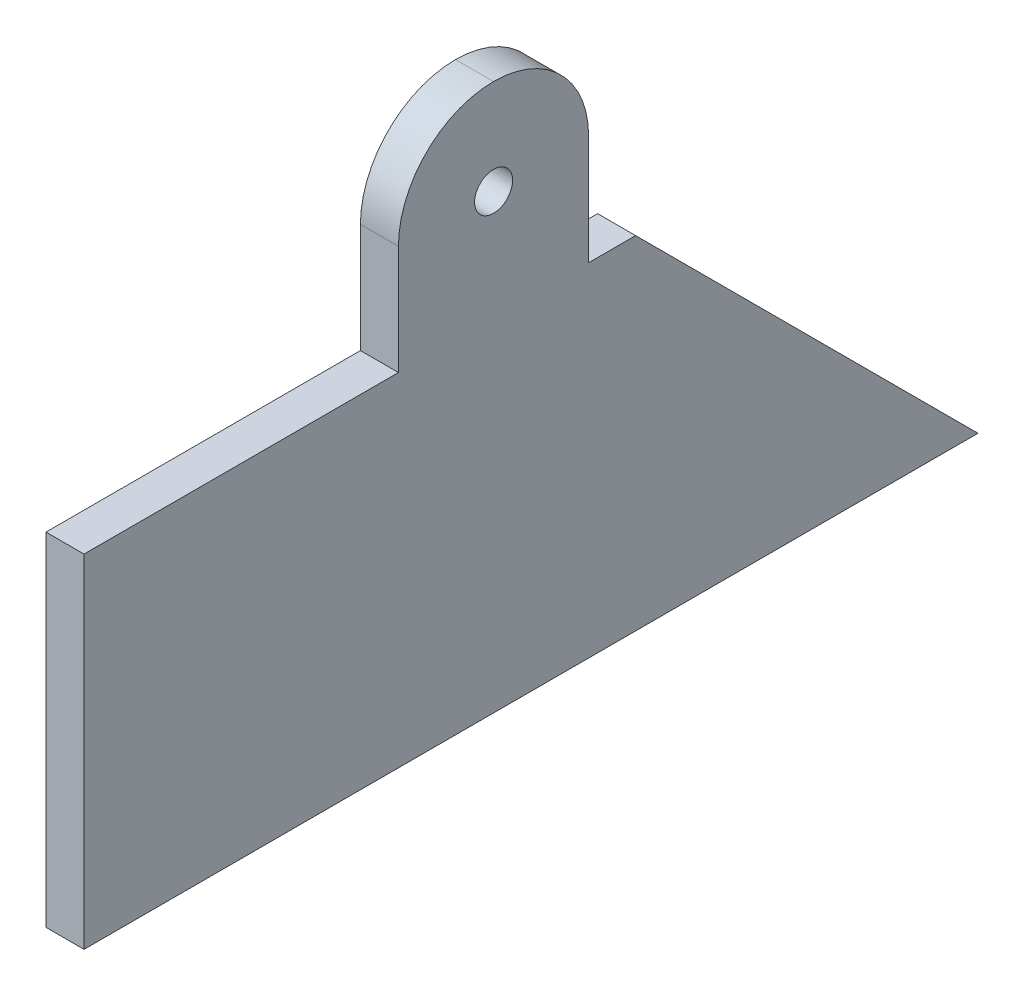
SolidWorks part; units mm, degrees
material "1060 Alloy"
ref_plane "Front Plane" through (0, 0, 0) normal (0, 0, 1) x (1, 0, 0)
ref_plane "Top Plane" through (0, 0, 0) normal (0, 1, 0) x (1, 0, 0)
ref_plane "Right Plane" through (0, 0, 0) normal (1, 0, 0) x (0, 0, -1)
sketch "Sketch1" plane through (0, 0, 0) normal (1, 0, 0) x (0, 0, -1)
  line L0 (0, 0) -> (298.45, 0)
  line L1 (0, 0) -> (0, 114.3)
  line L2 (298.45, 0) -> (184.15, 114.3)
  line L3 (0, 114.3) -> (184.15, 114.3)
  dimension "D1" = 298.45
  dimension "D2" = 114.3
  dimension "D3" = 45
extrude "main" add sketch "Sketch1" along normal blind 12.7 contours L2 L3 L1 L0
sketch "Sketch2" plane through (0, 114.3, 0) normal (0, 1, 0) x (1, 0, 0)
  line L0 (12.7, 0) -> (12.7, 184.15) construction
  line L1 (0, 104.968) -> (12.7, 104.968)
  line L2 (0, 104.968) -> (0, 168.468)
  line L3 (0, 168.468) -> (12.7, 168.468)
  line L4 (12.7, 104.968) -> (12.7, 168.468)
  line L5 (0, 104.968) -> (12.7, 168.468) construction
  line L6 (0, 168.468) -> (12.7, 104.968) construction
  line L7 (0, 0) -> (0, 184.15) construction
  line L8 (12.7, 184.15) -> (0, 184.15) construction
  point P0 (6.35, 136.718)
  dimension "D1" = 63.5
  dimension "D2" = 47.432
extrude "stand" add sketch "Sketch2" along normal blind 68.2625
sketch "Sketch3" plane through (12.7, 0, 0) normal (1, 0, 0) x (0, 0, -1)
  line L0 (104.968, 182.5625) -> (104.968, 114.3) construction
  line L1 (104.968, 182.5625) -> (168.468, 182.5625) construction
  circle A0 centre (136.718, 150.8125) radius 6.35
  dimension "D1" = 12.7
  dimension "D2" = 31.75
  dimension "D3" = 31.75
extrude "axle" cut sketch "Sketch3" against normal up to surface (12.7 mm away) up to face at (0, 102.7906, -128.684)
fillet "Fillet1" radius 31.75 1 edges at (6.35, 182.5625, -168.468) type face fillet first side face at (6.35, 148.4313, -168.468) second side face at (6.35, 182.5625, -136.718)
fillet "Fillet2" radius 31.75 1 edges at (6.35, 182.5625, -104.968) type face fillet first side face at (6.35, 182.5625, -120.843) second side face at (6.35, 148.4313, -104.968)
equation "\"D2@Sketch3\"=\"D1@Sketch2\"/2"
equation "\"D3@Sketch3\"=\"D2@Sketch3\""
